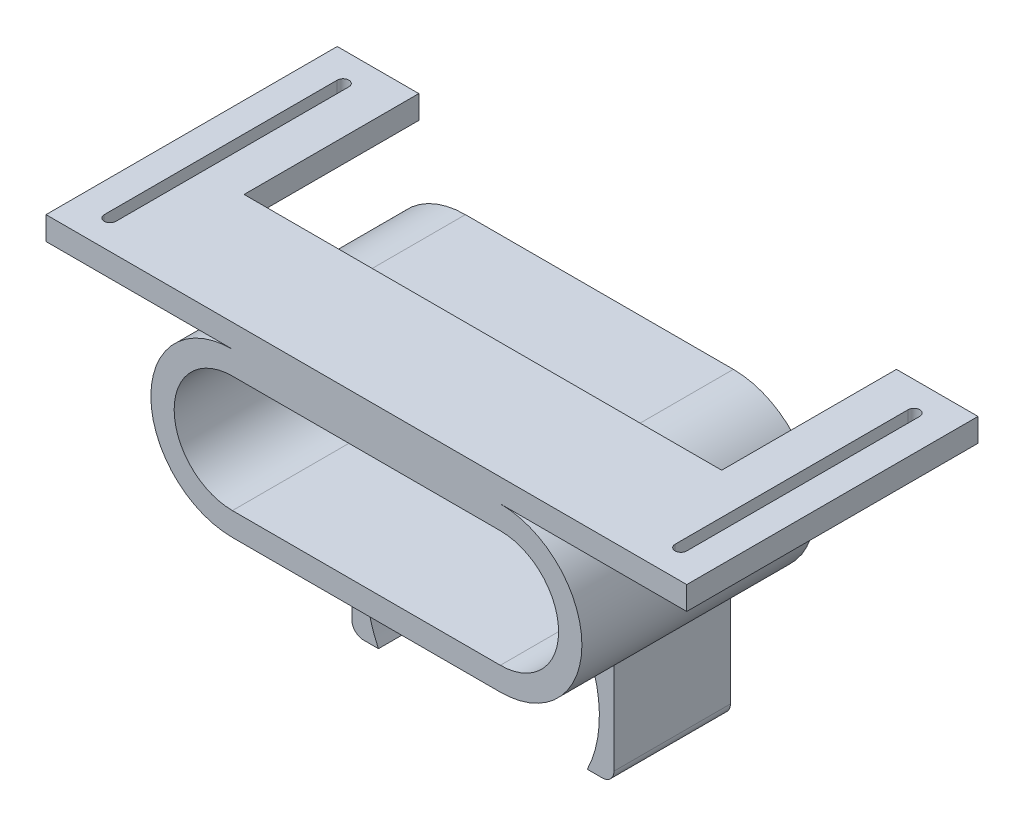
SolidWorks part; units mm, degrees
ref_plane "Front Plane" through (0, 0, 0) normal (0, 0, 1) x (1, 0, 0)
ref_plane "Top Plane" through (0, 0, 0) normal (0, 1, 0) x (1, 0, 0)
ref_plane "Right Plane" through (0, 0, 0) normal (1, 0, 0) x (0, 0, -1)
sketch "Sketch1" plane through (0, 0, 0) normal (0, 0, 1) x (1, 0, 0)
  line L0 (-16.5, 0) -> (16.5, 0) construction
  line L1 (18.15, 0) -> (-18.15, 0) construction
  line L2 (0, -5.5) -> (0, 5.5) construction
  line L3 (-11.5, 5) -> (11.5, 5)
  line L4 (11.5, -5) -> (-11.5, -5)
  line L5 (-11.5, 7) -> (11.5, 7)
  line L6 (11.5, -7) -> (-11.5, -7)
  arc A0 (11.5, -5) -> (11.5, 5) centre (11.5, 0) ccw
  arc A1 (-11.5, 5) -> (-11.5, -5) centre (-11.5, 0) ccw
  arc A2 (11.5, -7) -> (11.5, 7) centre (11.5, 0) ccw
  arc A3 (-11.5, 7) -> (-11.5, -7) centre (-11.5, 0) ccw
  point P5 (0, 0)
  dimension "D2" = 10
  dimension "D3" = 2
  dimension "D1" = 33
extrude "Boss-Extrude1" add sketch "Sketch1" along normal blind 20
sketch "Sketch2" plane through (0, 0, 0) normal (0, 0, -1) x (-1, 0, 0)
  line L0 (11.25, -7) -> (6.75, -7)
  line L1 (11.5, -7) -> (-11.5, -7) construction
  line L2 (0, 11) -> (0, -11) construction
  line L3 (-10, -14.5) -> (10, -14.5) construction
  line L4 (-11.25, -19) -> (-8.9626, -19)
  line L5 (-11.25, -19) -> (-11.25, -7)
  line L6 (11.25, -19) -> (11.25, -7)
  line L7 (-6.75, -7) -> (-11.25, -7)
  line L8 (8.9626, -19) -> (11.25, -19)
  line L9 (-6.75, -7) -> (6.75, -7) construction
  arc A1 (8.9626, -19) -> (6.75, -7) centre (-0.2788, -14.5) ccw
  arc A2 (-6.75, -7) -> (-8.9626, -19) centre (0.2788, -14.5) ccw
  point P4 (0, -7)
  point P9 (0, -14.5)
  dimension "D1" = 13.5
  dimension "D2" = 7.5
  dimension "D3" = 20
  dimension "D4" = 12
  dimension "D5" = 22.5
extrude "Boss-Extrude2" add sketch "Sketch2" against normal blind 10
fillet "Fillet1" radius 3 2 edges at (-11.25, -7, 5) (11.25, -7, 5)
fillet "Fillet2" radius 1 4 edges at (-6.75, -7, 5) (6.75, -7, 5) (11.25, -19, 5) (-11.25, -19, 5)
sketch "Sketch3" plane through (0, 7, 0) normal (0, 1, 0) x (1, 0, 0)
  line L0 (11.5, -20) -> (-11.5, -20) construction
  line L1 (-27.5, -20) -> (27.5, -20)
  line L3 (-20.5, -10) -> (20.5, -10)
  line L5 (0, -11) -> (0, 11) construction
  line L8 (-27.5, -20) -> (-27.5, 5)
  line L9 (-27.5, 5) -> (-20.5, 5)
  line L10 (-20.5, -10) -> (-20.5, 5)
  line L12 (27.5, -20) -> (27.5, 5)
  line L13 (27.5, 5) -> (20.5, 5)
  line L14 (20.5, -10) -> (20.5, 5)
  point P1 (27.5, 7.8196)
  point P2 (27.743, -20)
  point P6 (0, -10)
  point P15 (-27.2451, -20)
  dimension "D1" = 55
  dimension "D2" = 10
  dimension "D3" = 25
  dimension "D4" = 7
extrude "Boss-Extrude4" add sketch "Sketch3" along normal blind 2 contours L8 L9 L10 L3 L14 L13 L12 L1
sketch "Sketch4" plane through (0, 7, 0) normal (0, -1, 0) x (1, 0, 0)
  line L0 (-24.5, 17.5) -> (-24.5, -2.5) construction
  line L1 (-24, 17.5) -> (-24, -2.5)
  line L2 (-25, 17.5) -> (-25, -2.5)
  line L3 (-24.5, 17.5) -> (-24.5, 20) construction
  line L4 (-27.5, 20) -> (-11.5, 20) construction
  line L5 (-24.5, -2.5) -> (-24.5, -5) construction
  line L6 (-27.5, -5) -> (-20.5, -5) construction
  line L7 (0, -11) -> (0, 11) construction
  arc A0 (-24, 17.5) -> (-25, 17.5) centre (-24.5, 17.5) ccw
  arc A1 (-25, -2.5) -> (-24, -2.5) centre (-24.5, -2.5) ccw
  point P2 (-24.5, 7.5)
  dimension "D1" = 0.5
  dimension "D2" = 20
  dimension "D3" = 24.5
extrude "Cut-Extrude1" cut sketch "Sketch4" against normal up to next
mirror "Mirror1" about plane through (0, 0, 0) normal (1, 0, 0) of "Cut-Extrude1"
